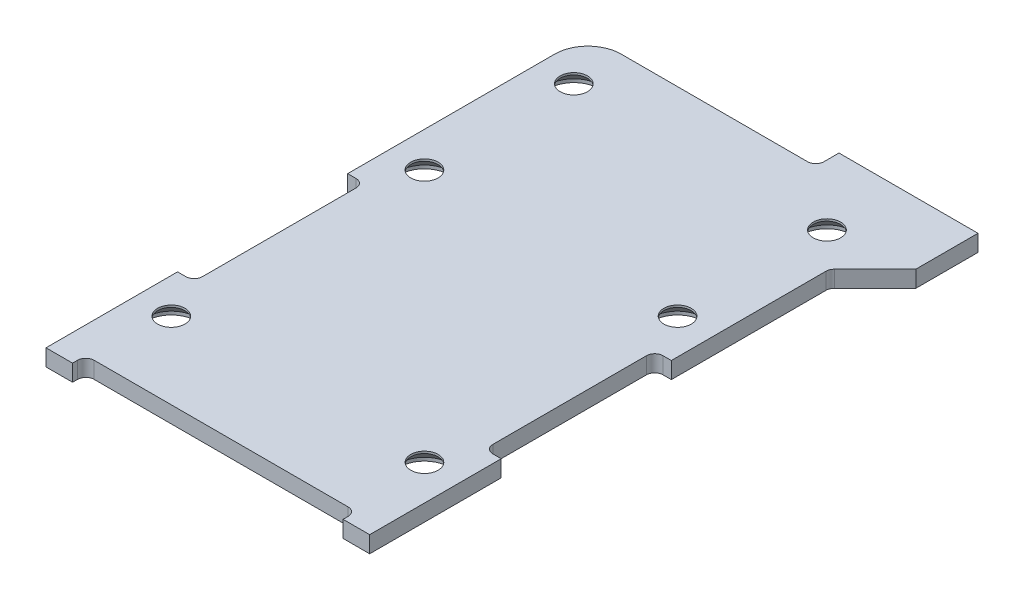
SolidWorks part; units mm, degrees
ref_plane "Front Plane" through (0, 0, 0) normal (0, 0, 1) x (1, 0, 0)
ref_plane "Top Plane" through (0, 0, 0) normal (0, 1, 0) x (1, 0, 0)
ref_plane "Right Plane" through (0, 0, 0) normal (1, 0, 0) x (0, 0, -1)
sketch "Sketch1" plane through (0, 0, 0) normal (0, 1, 0) x (1, 0, 0)
  line L1 (-18, 31.1) -> (18, 31.1)
  line L2 (-18, 31.1) -> (-18, -31.1)
  line L3 (-18, -31.1) -> (18, -31.1)
  line L4 (18, 31.1) -> (18, -31.1)
  line L5 (-18, 31.1) -> (18, -31.1) construction
  line L6 (-18, -31.1) -> (18, 31.1) construction
  point P0 (0, 0)
  dimension "D1" = 36
  dimension "D2" = 62.2
extrude "Base shape" add sketch "Sketch1" along normal blind 2
sketch "Sketch2" plane through (0, 2, 0) normal (0, 1, 0) x (1, 0, 0)
  line L0 (0, 31.1) -> (0, -31.1) construction
  line L1 (18, 31.1) -> (-18, 31.1) construction
  line L2 (-18, -31.1) -> (18, -31.1) construction
  line L4 (-18, 2.15) -> (-17.5, 2.15)
  line L5 (-18, 2.15) -> (-18, -18.35)
  line L6 (-18, -18.35) -> (-17.5, -18.35)
  line L7 (-17.5, 2.15) -> (-17.5, -18.35)
  line L8 (-17.5, -8.1) -> (-18, -8.1) construction
  line L9 (-15.25, -31.1) -> (-15.25, 31.1) construction
  line L11 (-18, -8.1) -> (18, -8.1) construction
  line L13 (15.25, 7.15) -> (15.25, -8.1) construction
  line L14 (15.25, 7.15) -> (0, 7.15) construction
  line L15 (18, -18.35) -> (17.5, -18.35)
  line L16 (17.5, 2.15) -> (17.5, -18.35)
  line L17 (18, 2.15) -> (17.5, 2.15)
  line L18 (18, 2.15) -> (18, -18.35)
  line L19 (18, -31.1) -> (18, 31.1) construction
  line L20 (-18, -31.1) -> (18, -31.1)
  line L21 (-18, -31.1) -> (-18, 14.9)
  line L22 (-18, 14.9) -> (18, 14.9)
  line L23 (18, -31.1) -> (18, 14.9)
  circle A0 centre (15.25, 7.15) radius 1.65
  circle A1 centre (15.25, -23.35) radius 1.65
  circle A2 centre (-15.25, 7.15) radius 1.65
  circle A3 centre (-15.25, -23.35) radius 1.65
  circle A4 centre (-15.25, 25.15) radius 1.65
  circle A5 centre (15.25, 25.15) radius 1.65
  line M13 (18, -31.1) -> (18, 31.1)
  line M15 (-18, 31.1) -> (-18, -31.1)
  dimension "D4" = 3.3
  dimension "D1" = 20.5
  dimension "D2" = 46
  dimension "D3" = 35
  dimension "D5" = 30.5
  dimension "D6" = 18
extrude "Cutouts" cut sketch "Sketch2" against normal up to next contours A2 | A0 | L17 L16 L15 M13 | L7 L4 L6 M15 | A3 | A1 | A4 | A5 region at (-17.75, 2, 8.1) region at (17.75, 2, 8.1) region at (15.25, 2, -7.15) region at (15.25, 2, 23.35) region at (-15.25, 2, -7.15) region at (-15.25, 2, 23.35)
sketch "Sketch3" plane through (0, 0, 0) normal (0, -1, 0) x (1, 0, 0)
  line L0 (18, -16.625) -> (19.5, -16.625) construction
  line L1 (19.5, 32.6) -> (-19.5, 32.6)
  line L2 (19.5, 32.6) -> (19.5, -32.6)
  line L3 (19.5, -32.6) -> (-19.5, -32.6)
  line L4 (-19.5, 32.6) -> (-19.5, -32.6)
  line L5 (19.5, 32.6) -> (-19.5, -32.6) construction
  line L6 (19.5, -32.6) -> (-19.5, 32.6) construction
  line L7 (0, -31.1) -> (0, -32.6) construction
  line L8 (-19.5, -31.1) -> (19.5, -31.1)
  line L9 (-19.5, -2.15) -> (19.5, -2.15)
  line L10 (-19.5, 18.35) -> (19.5, 18.35)
  line L11 (-19.5, 31.1) -> (19.5, 31.1)
  line L12 (-18, 18.35) -> (-17.5, 18.35)
  line L13 (-18, 31.1) -> (-18, 18.35)
  line L14 (18, 31.1) -> (-18, 31.1)
  line L15 (18, 18.35) -> (18, 31.1)
  line L16 (17.5, 18.35) -> (18, 18.35)
  line L17 (17.5, -2.15) -> (17.5, 18.35)
  line L18 (18, -2.15) -> (17.5, -2.15)
  line L19 (18, -31.1) -> (18, -2.15)
  line L20 (-18, -31.1) -> (18, -31.1)
  line L21 (-18, -2.15) -> (-18, -31.1)
  line L22 (-17.5, -2.15) -> (-18, -2.15)
  line L23 (-17.5, 18.35) -> (-17.5, -2.15)
  line L24 (-18, 18.35) -> (-17.5, 18.35)
  line L25 (-18, 31.1) -> (-18, 18.35)
  line L26 (18, 31.1) -> (-18, 31.1)
  line L27 (18, 18.35) -> (18, 31.1)
  line L28 (17.5, 18.35) -> (18, 18.35)
  line L29 (17.5, -2.15) -> (17.5, 18.35)
  line L30 (18, -2.15) -> (17.5, -2.15)
  line L31 (18, -31.1) -> (18, -2.15)
  line L32 (-18, -31.1) -> (18, -31.1)
  line L33 (-18, -2.15) -> (-18, -31.1)
  line L34 (-17.5, -2.15) -> (-18, -2.15)
  line L35 (-17.5, 18.35) -> (-17.5, -2.15)
  line L37 (24.7, -26.4) -> (24.7, -33.9) construction
  line L38 (7.95, -33.9) -> (24.7, -33.9) construction
  line L39 (7.95, -33.9) -> (7.95, -14.9) construction
  line L40 (24.7, -26.4) -> (19.5, -21.2) construction
  line L41 (24.7, -26.4) -> (24.7, -33.9)
  line L42 (7.95, -33.9) -> (24.7, -33.9)
  line L43 (7.95, -33.9) -> (7.95, -14.9)
  line L44 (24.7, -26.4) -> (19.5, -21.2)
  point P2 (0, 0)
  line M15 (18, -31.1) -> (18, -2.15)
  line M16 (18, 31.1) -> (-18, 31.1)
  line M17 (-18, 31.1) -> (-18, 18.35)
  line M35 (-18, -2.15) -> (-18, -31.1)
  line M36 (18, 18.35) -> (18, 31.1)
  dimension "D2" = 1.5
  dimension "D1" = 0
extrude "Extra size" add sketch "Sketch3" against normal up to surface (2 mm away) contours L9 L4 L8 M35 | L9 L8 L2 M15 | L11 L4 L10 M17 | L11 L10 L2 M36 | L4 L11 L2 L1 M16 | L43 L42 L41 L2 L3 | L43 L3 L2 L8 L32 region at (0, 0, 31.85) region at (18.75, 0, 24.725) region at (-18.75, 0, 24.725) region at (18.75, 0, -16.625) region at (-18.75, 0, -16.625) region at (20.0645, 0, -29.7415) region at (13.725, 0, -31.85) up to face at (15.25, 2, 25)
sketch "Sketch4" plane through (0, 0, 0) normal (0, 1, 0) x (1, 0, 0)
  circle A0 centre (-15.25, 25.15) radius 3
  circle A1 centre (15.25, 25.15) radius 3
  circle A2 centre (15.25, 7.15) radius 3
  circle A3 centre (-15.25, 7.15) radius 3
  circle A4 centre (-15.25, -23.35) radius 3
  circle A5 centre (15.25, -23.35) radius 3
  dimension "D1" = 6
extrude "Screw head cut" cut sketch "Sketch4" along normal blind 0.4
chamfer "Screw chamfer" distance 1.35 angle 45 6 edges at (-15.25, 0.4, 25) (15.25, 0.4, 25) (15.25, 0.4, -5.5) (15.25, 0.4, -23.5) (-15.25, 0.4, -23.5) (-15.25, 0.4, -5.5)
fillet "Front fillets" radius 4 1 edges at (-19.5, 1, -31.1)
sketch "Sketch6" plane through (0, 0, 32.6) normal (0, 0, 1) x (1, 0, 0)
  line L0 (19.5, 0) -> (-19.5, 0) construction
  line L1 (19.5, 2) -> (16.3, 2)
  line L2 (19.5, 2) -> (19.5, 0)
  line L3 (19.5, 0) -> (16.3, 0)
  line L4 (16.3, 2) -> (16.3, 0)
  line L5 (16.3, 10.2) -> (16.3, 2) construction
  line L6 (-16.3, 2) -> (-16.3, 10.2) construction
  line L7 (-19.5, 0) -> (-16.3, 0)
  line L8 (-19.5, 0) -> (-19.5, 2)
  line L9 (-19.5, 2) -> (-16.3, 2)
  line L10 (-16.3, 0) -> (-16.3, 2)
  line L11 (19.5, 2) -> (-19.5, 2) construction
extrude "Ledbar sides" add sketch "Sketch6" along normal up to surface (1.6 mm away)
fillet "Milling fillets" radius 1 8 edges at (-16.3, 1, 32.6) (16.3, 1, 32.6) (17.5, 1, -2.15) (17.5, 1, 18.35) (-17.5, 1, -2.15) (-17.5, 1, 18.35) (19.5, 1, -21.2) (7.95, 1, -31.1)
